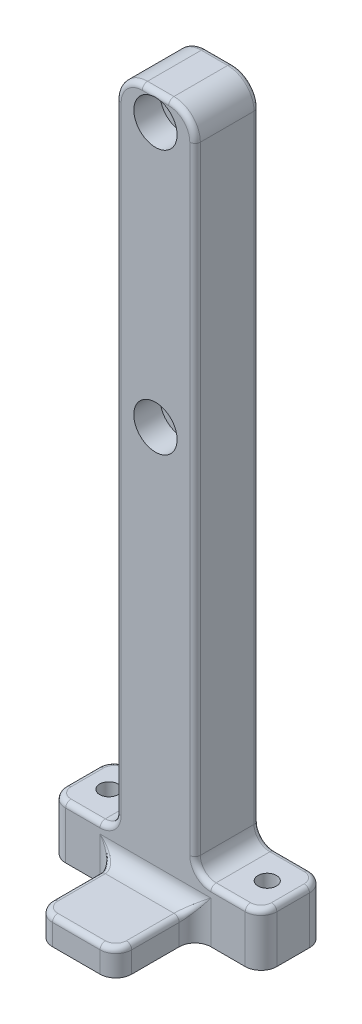
SolidWorks part; units mm, degrees
ref_plane "正面" through (0, 0, 0) normal (0, 0, 1) x (1, 0, 0)
ref_plane "平面" through (0, 0, 0) normal (0, 1, 0) x (1, 0, 0)
ref_plane "右側面" through (0, 0, 0) normal (1, 0, 0) x (0, 0, -1)
sketch "ｽｹｯﾁ1" plane through (0, 0, 0) normal (0, 0, 1) x (1, 0, 0)
  line L1 (7.5, -67.5) -> (-7.5, -67.5)
  line L2 (7.5, -67.5) -> (7.5, 67.5)
  line L3 (7.5, 67.5) -> (-7.5, 67.5)
  line L4 (-7.5, -67.5) -> (-7.5, 67.5)
  line L5 (7.5, -67.5) -> (-7.5, 67.5) construction
  line L6 (7.5, 67.5) -> (-7.5, -67.5) construction
  line L7 (-20, -57.5) -> (20, -57.5)
  line L8 (-20, -57.5) -> (-20, -67.5)
  line L9 (-20, -67.5) -> (20, -67.5)
  line L10 (20, -57.5) -> (20, -67.5)
  line L11 (-20, -57.5) -> (20, -67.5) construction
  line L12 (-20, -67.5) -> (20, -57.5) construction
  point P0 (0, 0)
  point P6 (0, -62.5)
  dimension "D1" = 15
  dimension "D2" = 135
  dimension "D3" = 10
  dimension "D4" = 40
  dimension "D5" = 0
  dimension "D6" = 0
extrude "ﾎﾞｽ - 押し出し1" add sketch "ｽｹｯﾁ1" along normal blind 12.1736 contours L2 L3 L4 L1 | L7 L10 L9 L8
sketch "ｽｹｯﾁ2" plane through (0, 0, 12.1736) normal (0, 0, 1) x (1, 0, 0)
  line L0 (20, -67.5) -> (-20, -67.5) construction
  circle A0 centre (0, 12.5) radius 4.1
  circle A1 centre (0, 62.5) radius 4.1
  dimension "D1" = 8.2
  dimension "D3" = 50
  dimension "D4" = 8.2
  dimension "D2" = 80
sketch "ｽｹｯﾁ3" plane through (0, -57.5, 0) normal (0, 1, 0) x (1, 0, 0)
  line L0 (20, -12.1736) -> (20, 0) construction
  line L1 (-20, -12.1736) -> (-20, 0) construction
  line L2 (7.5, 0) -> (20, 0) construction
  line L3 (-20, 0) -> (-7.5, 0) construction
  circle A0 centre (-15, -6) radius 1.75
  circle A1 centre (15, -6) radius 1.75
  dimension "D1" = 3.5
  dimension "D2" = 3.5
  dimension "D4" = 5
  dimension "D5" = 6
  dimension "D6" = 6
  dimension "D3" = 5
extrude "ｶｯﾄ - 押し出し1" cut sketch "ｽｹｯﾁ3" against normal through all
fillet "ﾌｨﾚｯﾄ2" radius 5 2 edges at (7.5, 67.5, 6.0868) (-7.5, 67.5, 6.0868)
extrude "ｶｯﾄ - 押し出し2" cut sketch "ｽｹｯﾁ2" against normal blind 5
sketch "ｽｹｯﾁ5" plane through (0, 0, 12.1736) normal (0, 0, 1) x (1, 0, 0)
  line L0 (0, -67.5) -> (0, 0) construction
  line L1 (20, -67.5) -> (-20, -67.5) construction
  line L5 (-7.5, -67.5) -> (7.5, -67.5)
  line L6 (-7.5, -67.5) -> (-7.5, -62.5)
  line L7 (-7.5, -62.5) -> (7.5, -62.5)
  line L8 (7.5, -67.5) -> (7.5, -62.5)
  dimension "D1" = 7.5
  dimension "D2" = 15
  dimension "D3" = 5
extrude "ﾎﾞｽ - 押し出し3" add sketch "ｽｹｯﾁ5" along normal blind 15
fillet "ﾌｨﾚｯﾄ16" radius 3 6 edges at (20, -62.5, 0) (20, -62.5, 12.1736) (-20, -62.5, 12.1736) (-20, -62.5, 0) (7.5, -57.5, 6.0868) (-7.5, -57.5, 6.0868)
fillet "ﾌｨﾚｯﾄ18" radius 3 3 edges at (0, -62.5, 12.1736)
fillet "ﾌｨﾚｯﾄ19" radius 3 2 edges at (7.5, -65, 27.1736) (-7.5, -65, 27.1736)
fillet "ﾌｨﾚｯﾄ20" radius 1 31 edges at (8.3787, -61.6213, 13.0523) (7.5, -62.5, 19.6736) (6.6213, -62.5, 26.2949) (0, -62.5, 27.1736) (-6.6213, -62.5, 26.2949) (-8.3787, -61.6213, 13.0523) (-8.3787, -56.6213, 12.1736) (-13.75, -57.5, 12.1736) (-19.1213, -57.5, 11.2949) (-20, -57.5, 6.0868) (-19.1213, -57.5, 0.8787) (-13.75, -57.5, 0) (-8.3787, -56.6213, 0) (-7.5, 4, 0) (-6.0355, 66.0355, 0) (0, 67.5, 0) (6.0355, 66.0355, 0) (7.5, 4, 0) (8.3787, -56.6213, 0) (13.75, -57.5, 0) (19.1213, -57.5, 0.8787) (20, -57.5, 6.0868) (19.1213, -57.5, 11.2949) (13.75, -57.5, 12.1736) (8.3787, -56.6213, 12.1736) (7.5, 4, 12.1736) (6.0355, 66.0355, 12.1736) (0, 67.5, 12.1736) (-6.0355, 66.0355, 12.1736) (-7.5, -62.5, 19.6736) (-7.5, 4, 12.1736)
